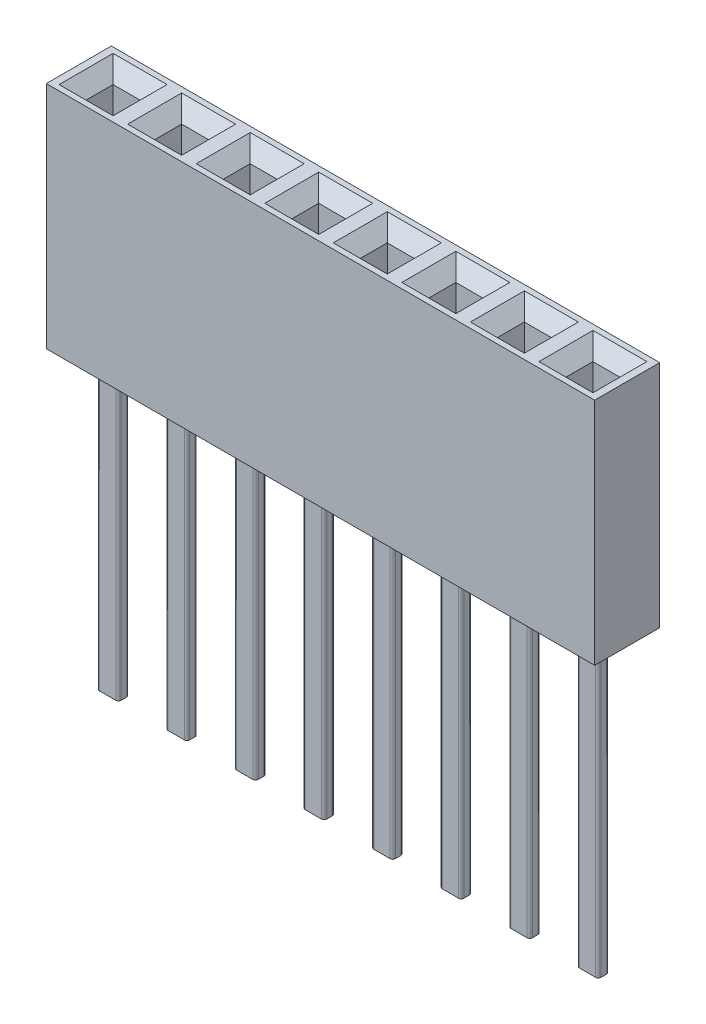
SolidWorks part; units mm, degrees
material "PA Type 6"
ref_plane "Front Plane" through (0, 0, 0) normal (0, 0, 1) x (1, 0, 0)
ref_plane "Top Plane" through (0, 0, 0) normal (0, 1, 0) x (1, 0, 0)
ref_plane "Right Plane" through (0, 0, 0) normal (1, 0, 0) x (0, 0, -1)
ref_plane "Plane1" through (0, -1.65, 0) normal (0, 1, 0) x (1, 0, 0)
sketch "Sketch2" plane through (0, 0, 0) normal (0, 1, 0) x (1, 0, 0)
  line L0 (0, -1.3255) -> (0, 1.3255) construction
  line L1 (-1.27, 1.205) -> (19.05, 1.205)
  line L2 (-1.27, 1.205) -> (-1.27, -1.205)
  line L3 (-1.27, -1.205) -> (19.05, -1.205)
  line L4 (19.05, 1.205) -> (19.05, -1.205)
  line L5 (-4.6805, 0) -> (4.6805, 0) construction
  dimension "D1" = 20.32
  dimension "D2" = 1.27
  dimension "D3" = 2.41
  dimension "D4" = 1.205
extrude "Boss-Extrude1" add sketch "Sketch2" along normal blind 8.51
sketch "Sketch5" plane through (0, 8.51, 0) normal (0, 1, 0) x (1, 0, 0)
  line L0 (-5.7805, 0) -> (5.7805, 0) construction
  line L1 (0.5, 0.5) -> (-0.5, 0.5)
  line L2 (0.5, 0.5) -> (0.5, -0.5)
  line L3 (0.5, -0.5) -> (-0.5, -0.5)
  line L4 (-0.5, 0.5) -> (-0.5, -0.5)
  line L5 (0, -1.3255) -> (0, 1.3255) construction
  dimension "D1" = 0.5
  dimension "D2" = 1
  dimension "D3" = 0.5
extrude "Cut-Extrude1" cut sketch "Sketch5" against normal blind 5
chamfer "Chamfer1" distance 0.5 angle 45 4 edges at (-0.5, 8.51, 0) (0, 8.51, 0.5) (0.5, 8.51, 0) (0, 8.51, -0.5)
pattern_linear "LPattern3" count 8 spacing 2.54 along (1, 0, 0) of "Chamfer1", "Cut-Extrude1"
sketch "Sketch8" plane through (0, 0, 0) normal (0, 1, 0) x (1, 0, 0)
  line L0 (0, -1.3255) -> (0, 1.3255) construction
  line L1 (-0.3, -0.2) -> (0.3, -0.2)
  line L2 (-0.4, -0.1) -> (-0.4, 0.1)
  line L3 (-0.3, 0.2) -> (0.3, 0.2)
  line L4 (0.4, -0.1) -> (0.4, 0.1)
  line L5 (-4.6805, 0) -> (4.6805, 0) construction
  arc A0 (-0.3, -0.2) -> (-0.4, -0.1) centre (-0.3, -0.1) cw
  arc A1 (0.3, -0.2) -> (0.4, -0.1) centre (0.3, -0.1) ccw
  arc A2 (0.3, 0.2) -> (0.4, 0.1) centre (0.3, 0.1) cw
  arc A3 (-0.4, 0.1) -> (-0.3, 0.2) centre (-0.3, 0.1) cw
  point P10 (-0.4, -0.2)
  point P13 (0.4, -0.2)
  point P16 (0.4, 0.2)
  dimension "D5" = 0.1
  dimension "D1" = 0.4
  dimension "D2" = 0.8
  dimension "D3" = 0.4
  dimension "D4" = 0.2
extrude "Boss-Extrude2" add sketch "Sketch8" against normal blind 11
sketch "Sketch10" plane through (0, -1.65, 0) normal (0, 1, 0) x (1, 0, 0)
  line L0 (0, -0.25) -> (0, 0.25) construction
  line L1 (0, -1.3255) -> (0, 1.3255) construction
  line L2 (-0.75, -0.25) -> (-0.75, 0.25)
  line L3 (0.75, -0.25) -> (0.75, 0.25)
  line L4 (-5.7805, 0) -> (5.7805, 0) construction
  arc A0 (-0.75, -0.25) -> (0.75, -0.25) centre (0, -0.25) ccw
  arc A1 (0.75, 0.25) -> (-0.75, 0.25) centre (0, 0.25) ccw
  point P5 (0, 0)
  dimension "D1" = 1.5
  dimension "D2" = 0.5
extrude "Boss-Extrude3" [suppressed] add sketch "Sketch10" along normal blind 0.1
fillet "Fillet2" [suppressed] radius 0.4
pattern_linear "LPattern1" count 8 spacing 2.54 along (1, 0, 0) of "Boss-Extrude2", "Fillet2", "Boss-Extrude3"
ref_axis "Axis1" through (0, -2.5255, 0) along (0, 1, 0)
equation "\"D1@Sketch2\"=2.54 * 8"
